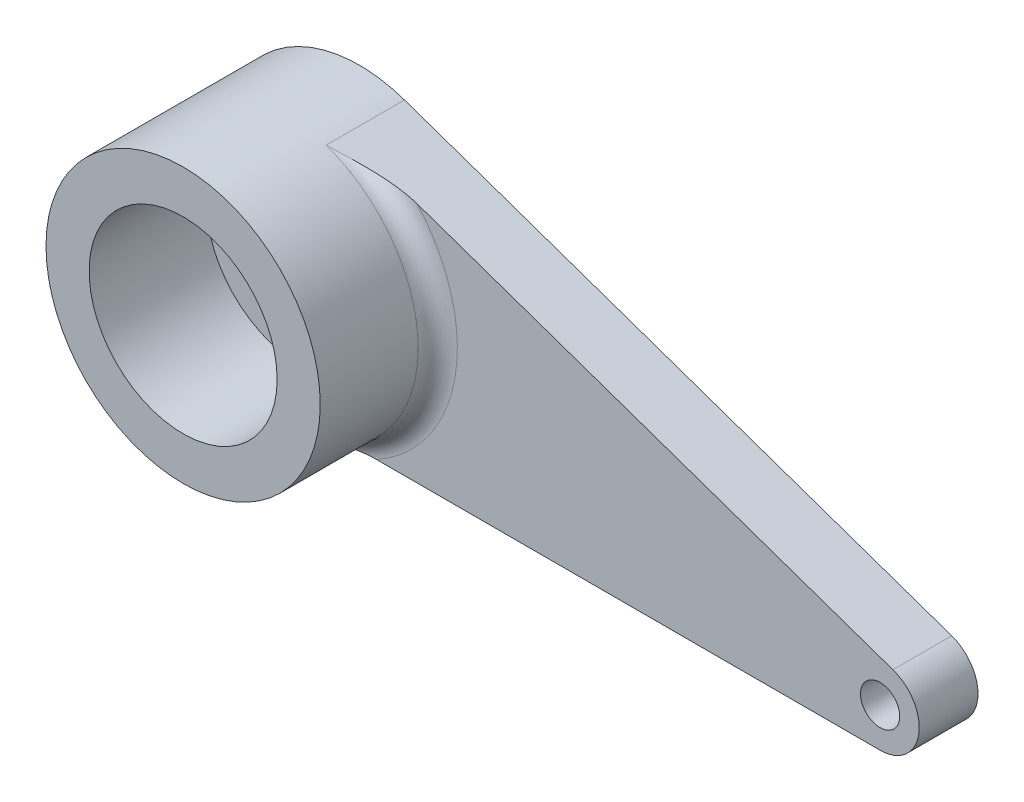
SolidWorks part; units mm, degrees
ref_plane "前视基准面" through (0, 0, 0) normal (0, 0, 1) x (1, 0, 0)
ref_plane "上视基准面" through (0, 0, 0) normal (0, 1, 0) x (1, 0, 0)
ref_plane "右视基准面" through (0, 0, 0) normal (1, 0, 0) x (0, 0, -1)
sketch "草图1" plane through (0, 0, 0) normal (0, 0, 1) x (1, 0, 0)
  line L0 (1.1503, 3.3056) -> (15.1189, -1.5556)
  line L1 (0, -3.5) -> (14.7902, -3.5)
  arc A0 (1.1503, 3.3056) -> (0, -3.5) centre (0, 0) ccw
  arc A1 (14.7902, -3.5) -> (15.1189, -1.5556) centre (14.7902, -2.5) ccw
  circle A2 centre (0, 0) radius 1
  circle A3 centre (14.7902, -2.5) radius 0.5
  dimension "D1" = 3.5
  dimension "D2" = 1
  dimension "D4" = 1
  dimension "D5" = 2
  dimension "D3" = 15
extrude "凸台-拉伸1" add sketch "草图1" along normal blind 1.5
sketch "草图2" plane through (0, 0, 1.5) normal (0, 0, 1) x (1, 0, 0)
  circle A0 centre (0, 0) radius 3.5
  circle A1 centre (0, 0) radius 2.4
  dimension "D1" = 7
  dimension "D2" = 4.8
extrude "凸台-拉伸2" add sketch "草图2" along normal blind 3
fillet "圆角1" radius 0.5 1 edges
